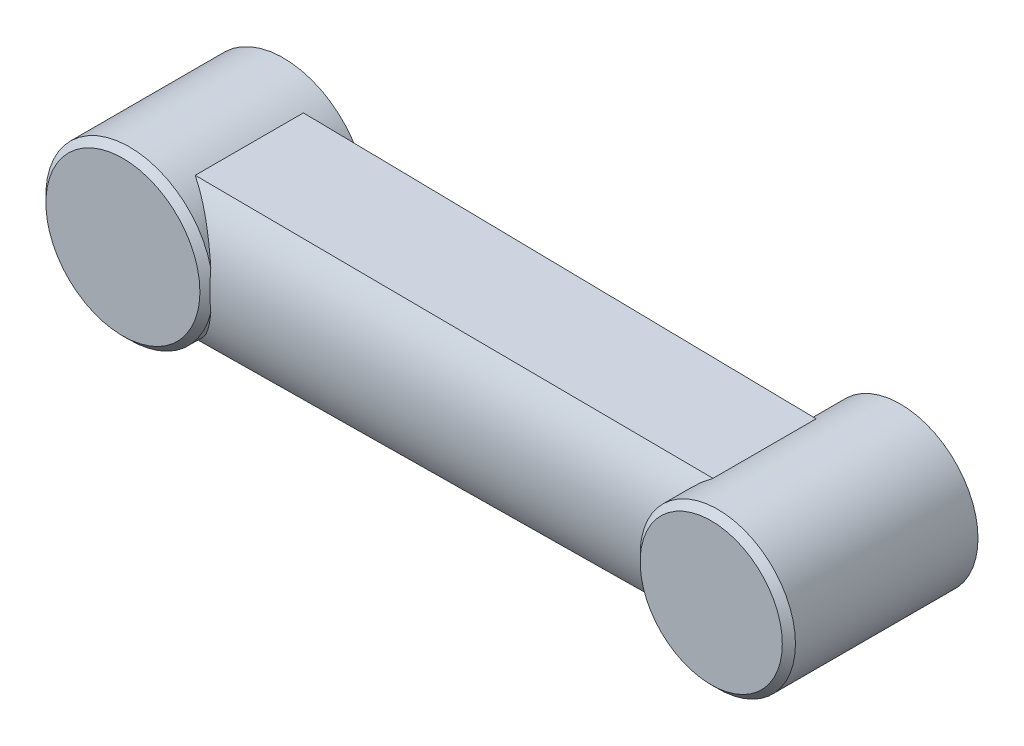
SolidWorks part; units mm, degrees
ref_plane "Front Plane" through (0, 0, 0) normal (0, 0, 1) x (1, 0, 0)
ref_plane "Top Plane" through (0, 0, 0) normal (0, 1, 0) x (1, 0, 0)
ref_plane "Right Plane" through (0, 0, 0) normal (1, 0, 0) x (0, 0, -1)
sketch "Sketch1" plane through (0, 0, 0) normal (0, 0, 1) x (1, 0, 0)
  circle A0 centre (0, 0) radius 63.5
  dimension "D1" = 127
extrude "Boss-Extrude1" add sketch "Sketch1" along normal blind 61 and the other way blind 61
chamfer "Chamfer1" distance 5 angle 45 1 edges at (63.5, 0, 61)
ref_plane "Plane2" through (63.5, 0, 0) normal (1, 0, 0) x (0, 0, -1)
ref_plane "Plane1" through (398.5, 0, 0) normal (1, 0, 0) x (0, 0, -1)
ref_plane "Plane3" through (457.5, 0, 0) normal (1, 0, 0) x (0, 0, -1)
ref_plane "Plane4" through (0, 0, 72.5) normal (0, 0, 1) x (1, 0, 0)
sketch "Sketch6" plane through (0, 0, 0) normal (-1, 0, 0) x (0, 0, 1)
  line L6 (40, -54) -> (-42.5, -54)
  line L7 (-42.5, 54) -> (40, 54)
  arc A5 (-42.5, 54) -> (-42.5, -54) centre (44.9479, 0) ccw
  arc A6 (40, 54) -> (40, -54) centre (-34.1011, 0) cw
sketch "Sketch7" plane through (457.5, 0, 59) normal (-1, 0, 0) x (0, 0, 1)
  line L0 (-19.9754, -49.884) -> (-98.0246, -49.884)
  line L6 (-98.0246, 49.884) -> (-19.9754, 49.884)
  line L7 (-98.0246, 49.884) -> (-19.9754, -49.884) construction
  arc A9 (-98.0246, 49.884) -> (-98.0246, -49.884) centre (-12.9036, 0) ccw
  arc A10 (-19.9754, 49.884) -> (-19.9754, -49.884) centre (-91.9525, 0) cw
loft "Loft1" add profiles "Sketch6", "Sketch7" start constraint default end constraint default connector at (0, 54, 40) connector at (457.5, 49.884, 39.0246)
sketch "Sketch9" plane through (0, 0, 0) normal (0, 0, 1) x (1, 0, 0)
  line L0 (457.5, -49.884) -> (457.5, 49.884) construction
  circle A0 centre (457.5, 0) radius 59
extrude "Boss-Extrude2" add sketch "Sketch9" along normal blind 71.5 and the other way blind 72.2
ref_axis "Axis1" through (0, 0, 56) along (0, 0, -1)
chamfer "Chamfer2" distance 5 angle 45 1 edges at (516.5, 0, 71.5)
